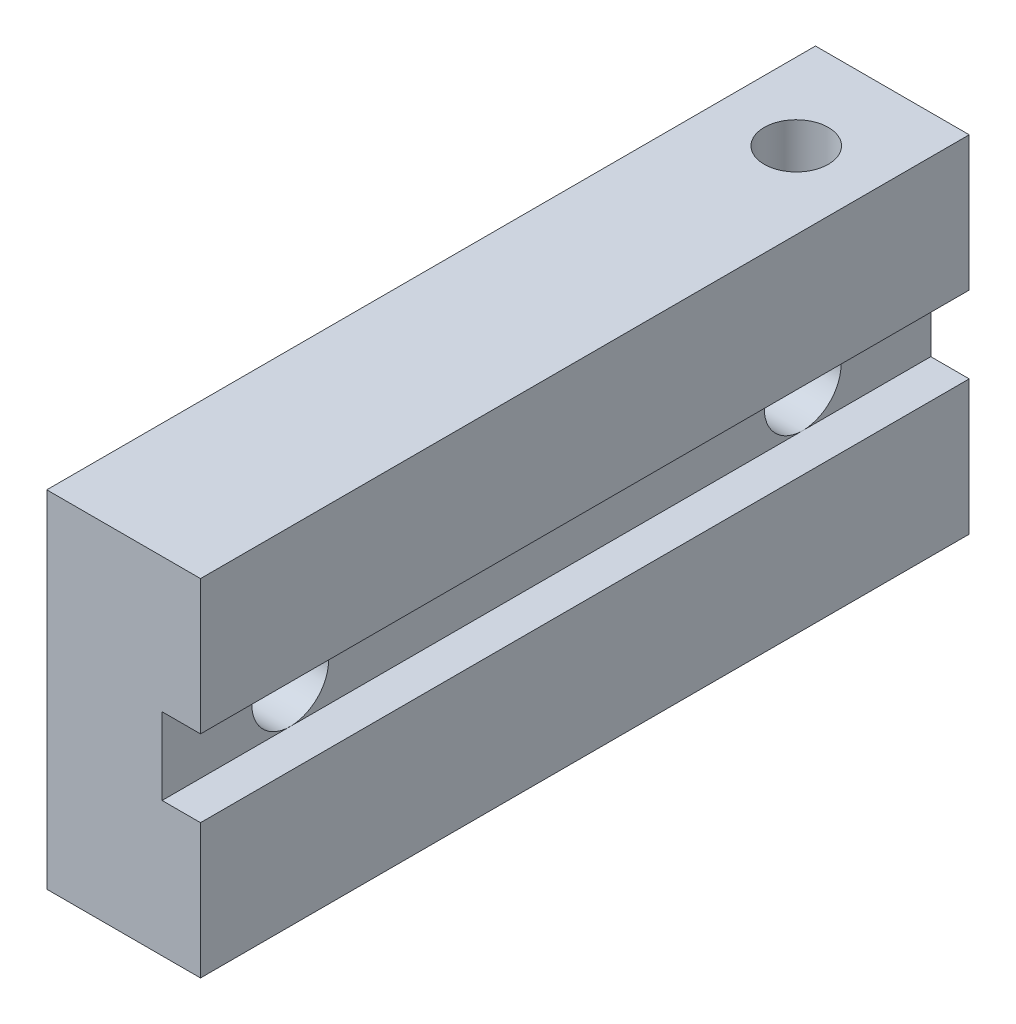
SolidWorks part; units mm, degrees
ref_plane "Front Plane" through (0, 0, 0) normal (0, 0, 1) x (1, 0, 0)
ref_plane "Top Plane" through (0, 0, 0) normal (0, 1, 0) x (1, 0, 0)
ref_plane "Right Plane" through (0, 0, 0) normal (1, 0, 0) x (0, 0, -1)
sketch "Sketch1" plane through (0, 0, 0) normal (1, 0, 0) x (0, 0, -1)
  line L0 (-30, 0) -> (30, 0) construction
  line L1 (30, -13.5) -> (-30, -13.5)
  line L2 (30, -13.5) -> (30, 13.5)
  line L3 (30, 13.5) -> (-30, 13.5)
  line L4 (-30, -13.5) -> (-30, 13.5)
  line L5 (30, -13.5) -> (-30, 13.5) construction
  line L6 (30, 13.5) -> (-30, -13.5) construction
  line L8 (30, -3) -> (-30, -3)
  line L9 (30, -3) -> (30, 3)
  line L10 (30, 3) -> (-30, 3)
  line L11 (-30, -3) -> (-30, 3)
  line L12 (30, -3) -> (-30, 3) construction
  line L13 (30, 3) -> (-30, -3) construction
  point P0 (0, 0)
  point P9 (0, 0)
  dimension "D1" = 60
  dimension "D2" = 27
  dimension "D3" = 6
extrude "Boss-Extrude1" add sketch "Sketch1" along normal blind 12 contours L10 L2 L3 L4 | L2 L8 L4 L1 region at (0, -8.25, 0) region at (0, 8.25, 0)
extrude "Boss-Extrude2" add sketch "Sketch1<4>" along normal blind 9 contours L2 L10 L4 L8 region at (0, 0, 0)
sketch "Sketch1<4>" plane through (0, 0, 0) normal (1, 0, 0) x (0, 0, -1) same geometry as "Sketch1"
sketch "Sketch8" plane through (0, 0, 0) normal (1, 0, 0) x (0, 0, -1)
  line L0 (-30, 0) -> (-20, 0) construction
  line L3 (-30, -3) -> (-30, 3) construction
  line L5 (30, 0) -> (20, 0) construction
  line L6 (30, -3) -> (30, 3) construction
  line L7 (-20, -2.1552) -> (-20, 2.1552) construction
  line L8 (20, 2.1552) -> (20, -2.1552) construction
hole_wizard "CBORE for M5 Pan Head Screw1" positions "3DSketch2" profile "Sketch11" counterbore size "M5" standard "DIN" end condition through all
sketch3d "3DSketch2"
  line L0 (0, 2.1552, -20) -> (0, -2.1552, -20) construction
  point P0 (0, 0, -20)
  point P3 (0, 0, 20)
  point P6 (0, 0, -20)
  point P10 (0, 0, -20)
  point P12 (0, 0, -20)
sketch "Sketch11" plane through (0, 0, -20) normal (0, 1, 0) x (0, 0, 1)
  line L0 (0, 0) -> (0, 12)
  line L1 (0, 12) -> (3, 12)
  line L3 (3, 12) -> (3, 3.7)
  line L4 (3, 3.7) -> (5.5, 3.7)
  line L5 (5.5, 3.7) -> (5.5, 0)
  line L7 (5.5, 0) -> (0, 0)
  line L11 (0, -6.35) -> (0, 107.95) construction
  dimension "Thru Hole Dia." = 6
  dimension "Thru Hole Depth" = 12
  dimension "C'Bore Dia." = 11
  dimension "C'Bore Depth" = 3.7
sketch "Sketch49" plane through (0, 13.5, 0) normal (0, 1, 0) x (1, 0, 0)
  line L0 (6, 30) -> (6, 22.5) construction
  line L1 (12, 30) -> (0, 30) construction
hole_wizard "Ø5.0 (5) Diameter Hole17" positions "3DSketch38" profile "Sketch60" hole size "Ø5.0" standard "DIN"
sketch3d "3DSketch38"
  point P0 (-4.9609, 0, -17.907)
  point P2 (-9.1023, 0, -17.47)
  point P4 (6, 13.5, -22.5)
sketch "Sketch60" plane through (6, 13.5, -22.5) normal (1, 0, 0) x (0, 0, 1)
  line L0 (0, 0) -> (0, 9.7022)
  line L1 (0, 9.7022) -> (2.5, 8.2)
  line L2 (2.5, 8.2) -> (2.5, 0)
  line L5 (2.5, 0) -> (0, 0)
  line L10 (0, 9.7022) -> (-2.5, 8.2) construction
  line L11 (0, -6.35) -> (0, 107.95) construction
  dimension "Hole Dia." = 5
  dimension "Hole Depth" = 8.2
  dimension "Drill Angle" = 118
sketch "Sketch61" plane through (0, 0, 0) normal (1, 0, 0) x (0, 0, -1)
  line L1 (-30, 13.5) -> (-24.3643, 13.5) construction
  line L2 (30, 13.5) -> (-30, 13.5) construction
